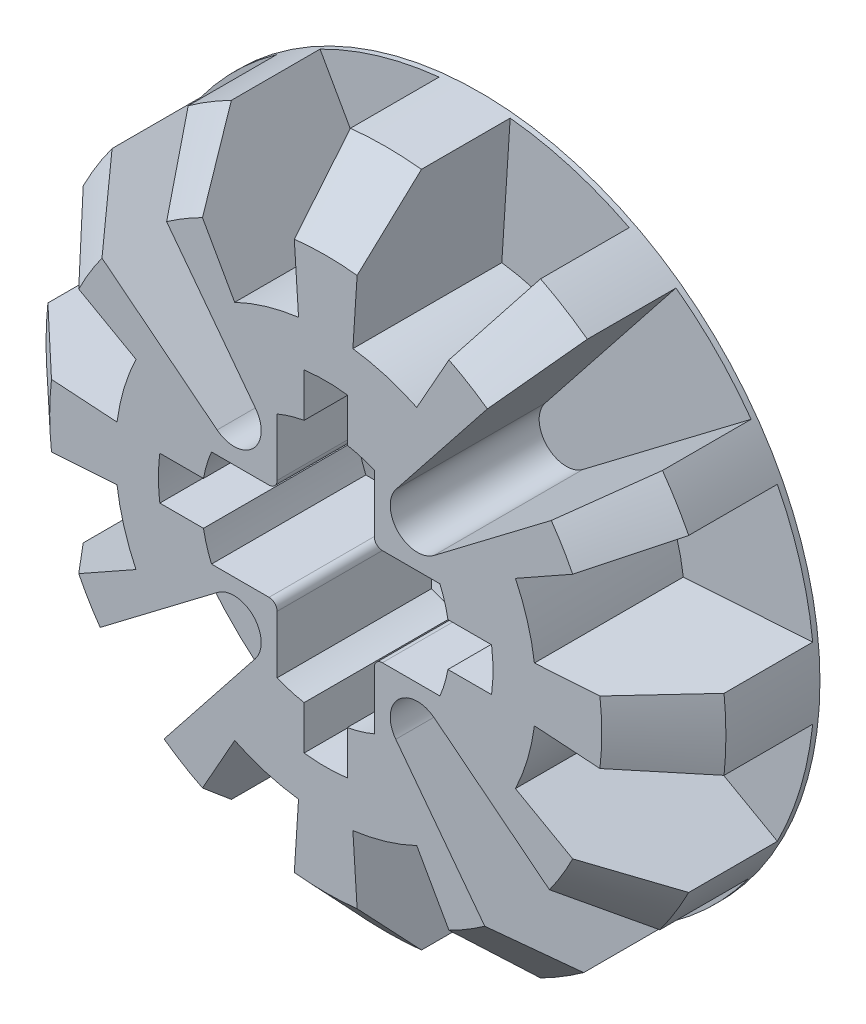
SolidWorks part; units mm, degrees
material "ABS"
ref_plane "Front Plane" through (0, 0, 0) normal (0, 0, 1) x (1, 0, 0)
ref_plane "Top Plane" through (0, 0, 0) normal (0, 1, 0) x (1, 0, 0)
ref_plane "Right Plane" through (0, 0, 0) normal (1, 0, 0) x (0, 0, -1)
sketch "Sketch1" plane through (0, 0, 0) normal (0, 0, 1) x (1, 0, 0)
  line L0 (-2.3, 0) -> (2.3, 0) construction
  line L1 (0, -2.3) -> (0, 2.3) construction
  line L2 (-2.1166, -0.9) -> (-1.05, -0.9)
  line L3 (0.9, -2.1166) -> (0.9, -1.05)
  line L4 (-2.1166, 0.9) -> (-1.05, 0.9)
  line L5 (-0.9, -2.1166) -> (-0.9, -1.05)
  line L6 (-2.3, -0.9) -> (2.3, -0.9) construction
  line L7 (-2.3, 0.9) -> (2.3, 0.9) construction
  line L8 (-0.9, -2.3) -> (-0.9, 2.3) construction
  line L9 (0.9, -2.3) -> (0.9, 2.3) construction
  line L10 (-0.9, 1.05) -> (-0.9, 2.1166)
  line L11 (1.05, 0.9) -> (2.1166, 0.9)
  line L12 (1.05, -0.9) -> (2.1166, -0.9)
  line L13 (0.9, 1.05) -> (0.9, 2.1166)
  line L14 (3.1, 0) -> (-3.1, 0) construction
  line L15 (0, 3.1) -> (0, -3.1) construction
  line L16 (-0.4, 3.0741) -> (-0.4, 2.265)
  line L17 (3.0741, 0.4) -> (2.265, 0.4)
  line L18 (0.4, 3.0741) -> (0.4, 2.265)
  line L19 (3.0741, -0.4) -> (2.265, -0.4)
  line L20 (3.1, -0.4) -> (-3.1, -0.4) construction
  line L21 (3.1, 0.4) -> (-3.1, 0.4) construction
  line L22 (-0.4, 3.1) -> (-0.4, -3.1) construction
  line L23 (0.4, 3.1) -> (0.4, -3.1) construction
  line L24 (-0.4, -2.265) -> (-0.4, -3.0741)
  line L25 (0.4, -2.265) -> (0.4, -3.0741)
  line L26 (-2.265, -0.4) -> (-3.0741, -0.4)
  line L27 (-2.265, 0.4) -> (-3.0741, 0.4)
  circle A0 centre (0, 0) radius 6.3
  circle A2 centre (0, 0) radius 3.35
  arc A19 (-0.9, -2.1166) -> (-0.4, -2.265) centre (0, 0) ccw
  circle A20 centre (0, 0) radius 3.1
  arc A21 (-2.1166, 0.9) -> (-2.265, 0.4) centre (0, 0) ccw
  arc A22 (0.9, 2.1166) -> (0.4, 2.265) centre (0, 0) ccw
  arc A23 (2.1166, -0.9) -> (2.265, -0.4) centre (0, 0) ccw
  arc A24 (-1.05, 0.9) -> (-0.9, 1.05) centre (-1.05, 1.05) ccw
  arc A25 (0.9, 1.05) -> (1.05, 0.9) centre (1.05, 1.05) ccw
  arc A26 (1.05, -0.9) -> (0.9, -1.05) centre (1.05, -1.05) ccw
  arc A27 (-0.9, -1.05) -> (-1.05, -0.9) centre (-1.05, -1.05) ccw
  circle A28 centre (0, 0) radius 3.1
  arc A29 (0.4, -2.265) -> (0.9, -2.1166) centre (0, 0) ccw
  arc A30 (-2.265, -0.4) -> (-2.1166, -0.9) centre (0, 0) ccw
  arc A31 (-0.4, 2.265) -> (-0.9, 2.1166) centre (0, 0) ccw
  arc A32 (2.265, 0.4) -> (2.1166, 0.9) centre (0, 0) ccw
  dimension "D1" = 12.6
  dimension "D2" = 4.6
  dimension "D3" = 6.2
  dimension "D6" = 0.9
  dimension "D4" = 6.7
  dimension "D7" = 0.15
  dimension "D8" = 6.2
  dimension "D5" = 0.9
  dimension "D9" = 0.4
  dimension "D10" = 0.4
extrude "Boss-Extrude1" add sketch "Sketch1" along normal blind 2.86 contours A31 L16 A20 L27 A21 L4 A24 L10 | A30 L26 A20 L24 A19 L5 A27 L2 | A29 L25 A20 L19 A23 L12 A26 L3 | A32 L17 A20 L18 A22 L13 A25 L11 | A2 A20 | A0 A2 region at (-1.6876, -1.6876, 0) region at (-1.6876, 1.6876, 0) region at (1.6876, -1.6876, 0) region at (1.6876, 1.6876, 0) region at (-6.1218, 0, 0) region at (-3.2552, 0, 0)
sketch "Sketch2" plane through (0, 0, 0) normal (0, 0, -1) x (-1, 0, 0)
  circle A0 centre (0, 0) radius 4.1
  circle A1 centre (0, 0) radius 3.1
  arc A3 (0.4, 3.0741) -> (-0.4, 3.0741) centre (0, 0) ccw construction
  dimension "D1" = 1
extrude "Boss-Extrude2" add sketch "Sketch2" along normal blind 1.01
sketch "Sketch3" plane through (0, 0, 2.86) normal (0, 0, 1) x (1, 0, 0)
  line L0 (-0.5035, 3.8674) -> (-0.6655, 6.374)
  line L1 (-2.9185, 5.7055) -> (-0.5035, 3.8674) construction
  line L2 (-1.6871, 3.5162) -> (-2.9185, 5.7055)
  line L3 (-2.9185, 5.7055) -> (-0.6655, 6.374)
  line L4 (-0.6655, 6.374) -> (-1.6871, 3.5162) construction
  line L5 (-3.1444, 6.1074) -> (0.1982, 0.164) construction
  line L6 (-0.7118, 7.0896) -> (-0.3781, 1.9255) construction
  line L7 (0.5587, -0.5587) -> (-5.7193, 5.7193) construction
  line L8 (-7.0896, 0.7118) -> (-1.9255, 0.3781) construction
  line L9 (-6.1074, 3.1444) -> (-0.164, -0.1982) construction
  line L10 (-6.374, 0.6655) -> (-3.5162, 1.6871) construction
  line L11 (-5.7055, 2.9185) -> (-3.8674, 0.5035) construction
  line L12 (-5.7055, 2.9185) -> (-6.374, 0.6655)
  line L13 (-3.5162, 1.6871) -> (-5.7055, 2.9185)
  line L14 (-3.8674, 0.5035) -> (-6.374, 0.6655)
  line L15 (2.0129, -1.3049) -> (5.0756, -3.7321)
  line L16 (5.0756, -3.7321) -> (3.8612, -5.3836)
  line L17 (3.8612, -5.3836) -> (1.2983, -2.0044)
  line L18 (2.0129, -1.3049) -> (3.8612, -5.3836) construction
  line L19 (1.2983, -2.0044) -> (5.0756, -3.7321) construction
  circle A0 centre (0, 0) radius 3.9
  circle A1 centre (0, 0) radius 1.9 construction
  circle A2 centre (0, 0) radius 6.3 construction
  arc A5 (1.05, -0.9) -> (0.9, -1.05) centre (1.05, -1.05) ccw construction
  arc A6 (1.2983, -2.0044) -> (2.0129, -1.3049) centre (1.6999, -1.6999) cw
  point P13 (0.9439, -0.9439)
  point P33 (1.3473, -1.3397)
  point P45 (2.5996, -2.5996)
  circle M17 centre (0, 0) radius 6.3
  dimension "D3" = 2.05
  dimension "D4" = 2.4
  dimension "D1" = 3.8
  dimension "D2" = 2.35
  dimension "D5" = 1
extrude "Cut-Extrude1" cut sketch "Sketch3" against normal blind 2.76 contours A0 L0 L2 M17 | A0 L17 L15 M17 | A6 L17 A0 L15 | A0 L13 L14 M17 region at (-1.4775, 4.9796, 2.86) region at (2.1151, -2.125, 2.86) region at (3.6193, -3.6611, 2.86) region at (-4.9796, 1.4775, 2.86)
pattern_circular "CirPattern1" count 4 over 360 about axis through (0, 0, 2.86) along (0, 0, 1) of "Cut-Extrude1"
sketch "Sketch5" plane through (0, 0, 0) normal (0, 1, 0) x (1, 0, 0)
  line L0 (0, 2.7979) -> (0, -4.1995) construction
  line L1 (-6.59, -3.11) -> (-6.59, -1.47)
  line L2 (-6.59, -1.47) -> (-4.85, -3.11)
  line L3 (-4.85, -3.11) -> (-6.59, -3.11)
  dimension "D1" = 4.85
  dimension "D2" = 6.59
  dimension "D3" = 1.47
  dimension "D4" = 3.11
revolve "Cut-Revolve1" cut sketch "Sketch5" angle 360 about L0
